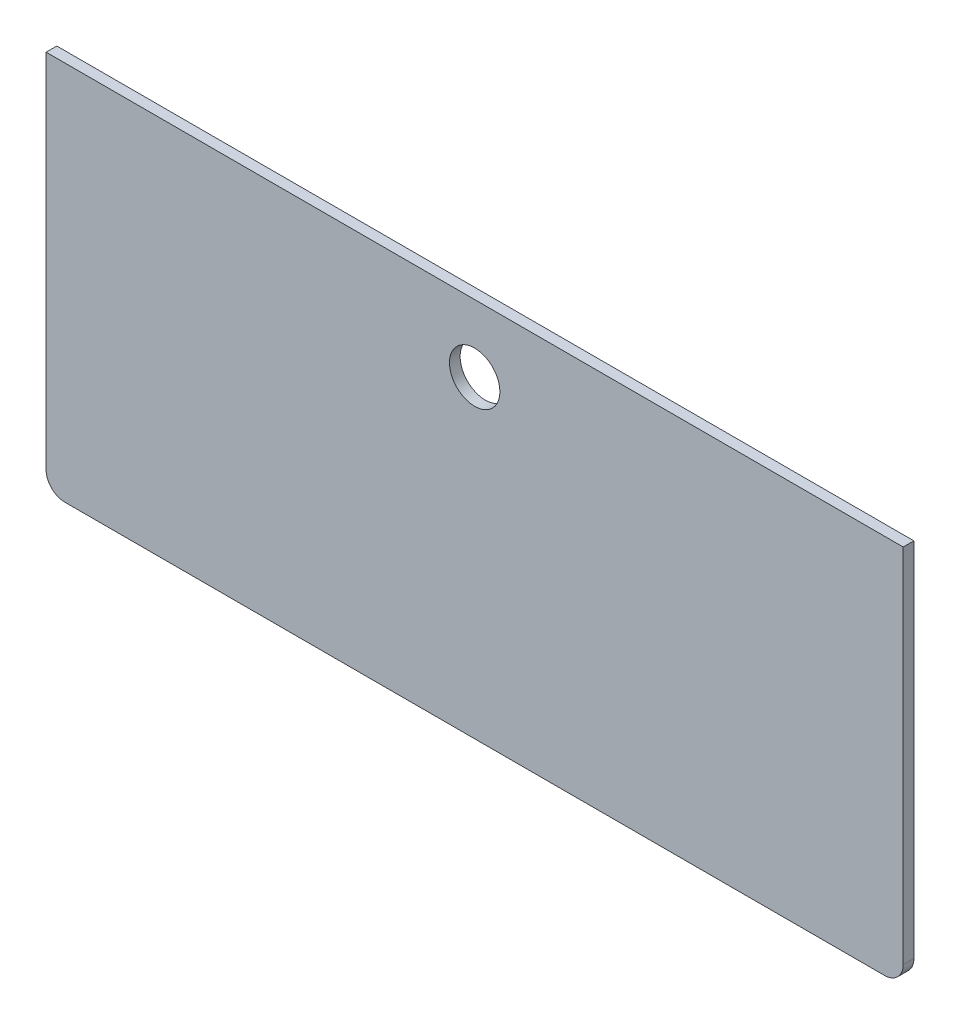
SolidWorks part; units mm, degrees
material "5052-H32"
ref_plane "Front Plane" through (0, 0, 0) normal (0, 0, 1) x (1, 0, 0)
ref_plane "Top Plane" through (0, 0, 0) normal (0, 1, 0) x (1, 0, 0)
ref_plane "Right Plane" through (0, 0, 0) normal (1, 0, 0) x (0, 0, -1)
sketch "Sketch1" plane through (0, 0, 0) normal (0, 0, 1) x (1, 0, 0)
  line L0 (-151.7654, 27.1868) -> (-151.7654, -85.9882)
  line L1 (-151.7654, -85.9882) -> (103.2346, -85.9882)
  line L2 (103.2346, -85.9882) -> (103.2346, 27.1868)
  line L3 (103.2346, 27.1868) -> (-151.7654, 27.1868)
  line L4 (-24.2654, 27.1868) -> (-24.2654, 7.1868) construction
  circle A0 centre (-24.2654, 7.1868) radius 7.5
  dimension "D4" = 15
  dimension "D1" = 113.175
  dimension "D2" = 255
  dimension "D3" = 20
extrude "Boss-Extrude1" add sketch "Sketch1" along normal blind 3.175
fillet "Fillet1" radius 5.5562 2 edges at (-151.7654, -85.9882, 1.5875) (103.2346, -85.9882, 1.5875)
equation "\"L\"= 385"
equation "\"W\"= 255"
equation "\"H\"= 110"
equation "\"Compartment Width\"= 80"
equation "\"T\"= 4.7625 * 2 / 3"
equation "\"Inside Fillet Radius\"= 5.55625"
equation "\"D1@Boss-Extrude1\"=\"T\""
equation "\"D1@Fillet1\"=\"Inside Fillet Radius\""
equation "\"Hole\"=15"
equation "\"D4@Sketch1\"=\"Hole\""
equation "\"D2@Sketch1\"=\"W\""
equation "\"D1@Sketch1\"=\"H\"+\"T\""
